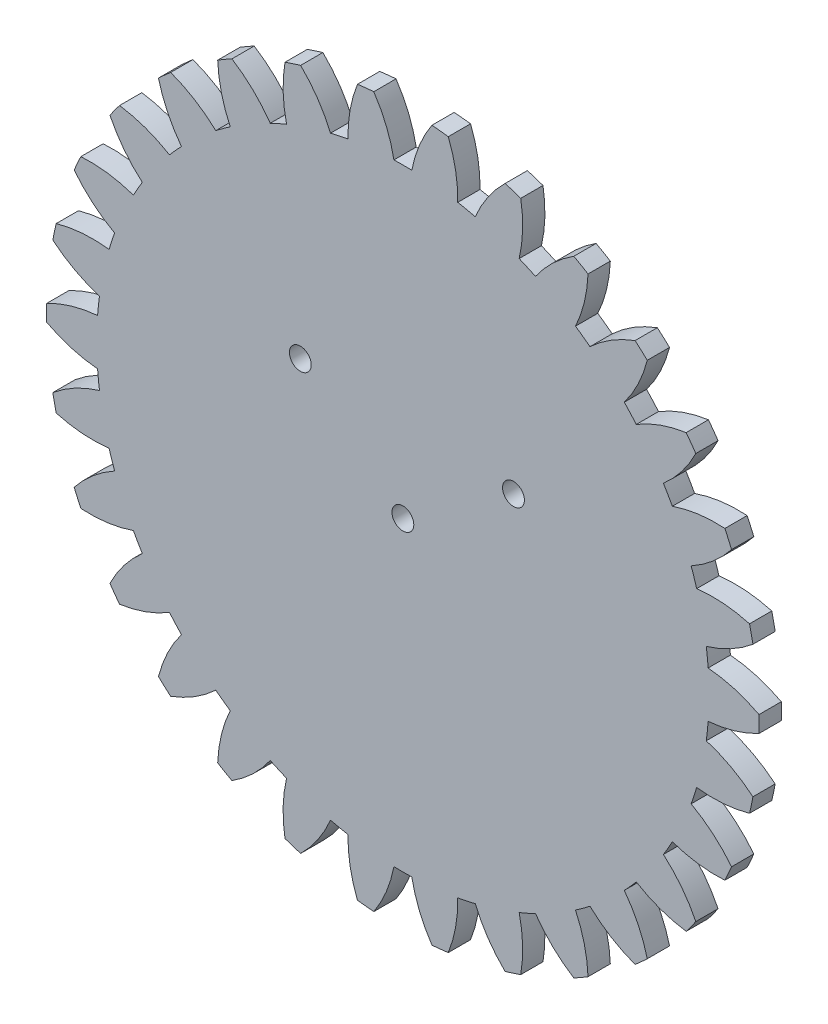
SolidWorks part; units mm, degrees
ref_plane "Front Plane" through (0, 0, 0) normal (0, 0, 1) x (1, 0, 0)
ref_plane "Top Plane" through (0, 0, 0) normal (0, 1, 0) x (1, 0, 0)
ref_plane "Right Plane" through (0, 0, 0) normal (1, 0, 0) x (0, 0, -1)
sketch "Sketch1" plane through (0, 0, 0) normal (0, 0, 1) x (1, 0, 0)
  line L0 (0, 0) -> (15.385, 23.3896) construction
  circle A0 centre (0, 0) radius 48
  dimension "D1" = 96
extrude "Boss-Extrude1" add sketch "Sketch1" along normal blind 3
sketch "Sketch2" plane through (0, 0, 3) normal (0, 0, 1) x (1, 0, 0)
  line L0 (0, 0) -> (0, 48) construction
  line L1 (0, 0) -> (-5.0174, 47.7371) construction
  line L2 (-2.3411, 44.9391) -> (-4.6973, 44.6914) construction
  circle A0 centre (0, 0) radius 41.25 construction
  circle A1 centre (0, 0) radius 42.2862 construction
  circle A2 centre (0, 0) radius 45 construction
  circle A5 centre (0, 0) radius 48 construction
  arc A6 (-1.2039, 41.2324) -> (1.2039, 41.2324) centre (0, 0) cw
  arc A7 (-3.9161, 47.84) -> (3.9161, 47.84) centre (0, 0) cw
  arc A8 (-3.9161, 47.84) -> (-1.2039, 41.2324) centre (-18.8807, 37.837) cw
  arc A9 (1.2039, 41.2324) -> (3.9161, 47.84) centre (18.8807, 37.837) cw
  dimension "D1" = 82.5
  dimension "D2" = 84.5723
  dimension "D3" = 90
  dimension "D5" = 18
  dimension "D6" = 18
  dimension "D4" = 6
  dimension "D7" = 2.3562
extrude "Cut-Extrude1" cut sketch "Sketch2" against normal through all
pattern_circular "CirPattern1" count 30 over 360 about axis through (0, 0, 3) along (0, 0, 1) of face at (-2.3945, 44.6041, 1.5) of face at (0, 41.2412, 1.5) of face at (2.3945, 44.6041, 1.5)
ref_axis "Axis1" through (0, 0, 0) along (0, 0, 1)
sketch "Sketch7" plane through (0, 0, 0) normal (0, 0, -1) x (-1, 0, 0)
  circle A0 centre (0, 0) radius 1.47
  dimension "D1" = 2.94
extrude "Cut-Extrude2" cut sketch "Sketch7" against normal through all contours A0
sketch "Sketch8" plane through (0, 0, 0) normal (0, 0, -1) x (-1, 0, 0)
  circle A0 centre (-14.9063, 10.311) radius 1.47
  circle A1 centre (13.8177, 11.7297) radius 1.47
  dimension "D1" = 2.94
  dimension "D2" = 2.94
extrude "Cut-Extrude3" cut sketch "Sketch8" against normal through all
equation "\"module\"= 3.0"
equation "\"teeth\"= 30"
equation "\"pressureAngle\"= 20deg"
equation "\"gearThickness\"= 3"
equation "\"addendumFactor\"= 1"
equation "\"dedendumFactor\"= 1.25"
equation "\"pitch\"= 1 / \"module\""
equation "\"pitchDiameter\"= \"teeth\" / \"pitch\""
equation "\"addendum\"= \"addendumFactor\" / \"pitch\""
equation "\"dedendum\"= \"dedendumFactor\" / \"pitch\""
equation "\"D1@Sketch1\"=\"pitchDiameter\" + 2 * \"addendum\""
equation "\"D1@Boss-Extrude1\"=\"gearThickness\""
equation "\"D1@Sketch2\"=\"pitchDiameter\" - 2 * \"dedendum\""
equation "\"D2@Sketch2\"=\"pitchDiameter\" * cos(\"pressureAngle\")"
equation "\"D3@Sketch2\"=\"pitchDiameter\""
equation "\"D4@Sketch2\"=180/\"teeth\""
equation "\"D5@Sketch2\"=\"pitchDiameter\"/5"
equation "\"D6@Sketch2\"=\"pitchDiameter\"/5"
equation "\"D7@Sketch2\"= PI / 2 / \"pitch\"/2"
equation "\"D1@CirPattern1\"=\"teeth\""
